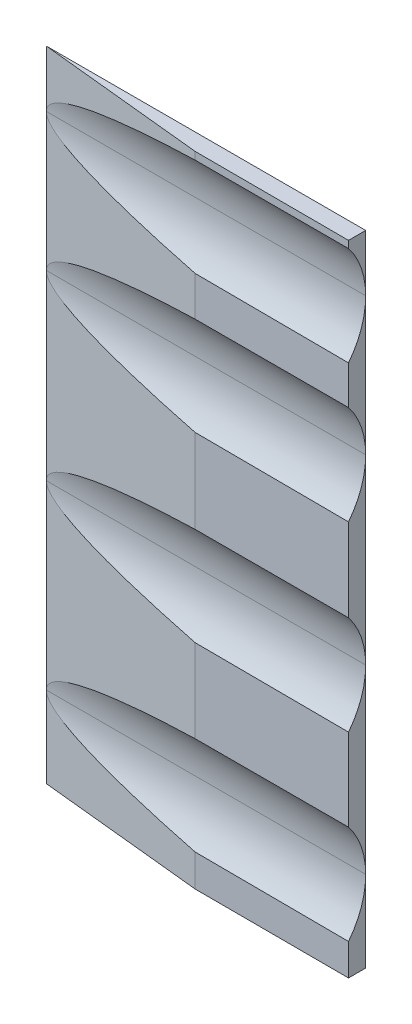
SolidWorks part; units mm, degrees
ref_plane "前视基准面" through (0, 0, 0) normal (0, 0, 1) x (1, 0, 0)
ref_plane "上视基准面" through (0, 0, 0) normal (0, 1, 0) x (1, 0, 0)
ref_plane "右视基准面" through (0, 0, 0) normal (1, 0, 0) x (0, 0, -1)
sketch "草图1" plane through (0, 0, 0) normal (0, 0, 1) x (1, 0, 0)
  line L1 (0, 0) -> (8, 0)
  line L2 (0, 0) -> (0, 16)
  line L3 (0, 16) -> (8, 16)
  line L4 (8, 0) -> (8, 16)
extrude "凸台-拉伸1" add sketch "草图1" along normal blind 2
sketch "草图3" plane through (0, 0, 0) normal (-1, 0, 0) x (0, 0, 1)
  line L0 (2, 16) -> (2, 0) construction
  line L1 (0.5893, 16) -> (2, 16)
  line L2 (2, 16) -> (2, 9.1331)
  line L3 (2, 4.0325) -> (2, 0.0325)
  line L4 (2, 8.573) -> (2, 4.573)
  arc A0 (2, 4.0325) -> (2, 0.0325) centre (2, 2.0325) ccw
  arc A1 (2, 8.573) -> (2, 4.573) centre (2, 6.573) ccw
  arc A2 (0.9872, 12.8577) -> (2, 9.1331) centre (2, 11.1331) ccw
  arc A3 (0.5893, 16) -> (0.9872, 12.8577) centre (2, 14.5823) ccw
extrude "切除-拉伸1" cut sketch "草图3" against normal up to surface (8 mm away) up to face at (8, 8, 1)
sketch "草图4" plane through (0, 0, 0) normal (0, -1, 0) x (1, 0, 0)
  line L5 (4.1484, 0.4219) -> (0, 0)
  line L7 (2.5983, 2.0289) -> (0, 2)
  line L8 (0, 2) -> (0, 0)
  line L9 (2.5983, 2.0289) -> (8.2859, 2.0289)
  line L11 (8.2859, 2.0289) -> (8, 0.4309)
  line L12 (8, 2) -> (8, 0) construction
  line L13 (8, 0.4309) -> (4.1484, 0.4219)
extrude "切除-拉伸3" cut sketch "草图4" against normal up to surface (16 mm away) up to face at (4, 16, 0.2946)
